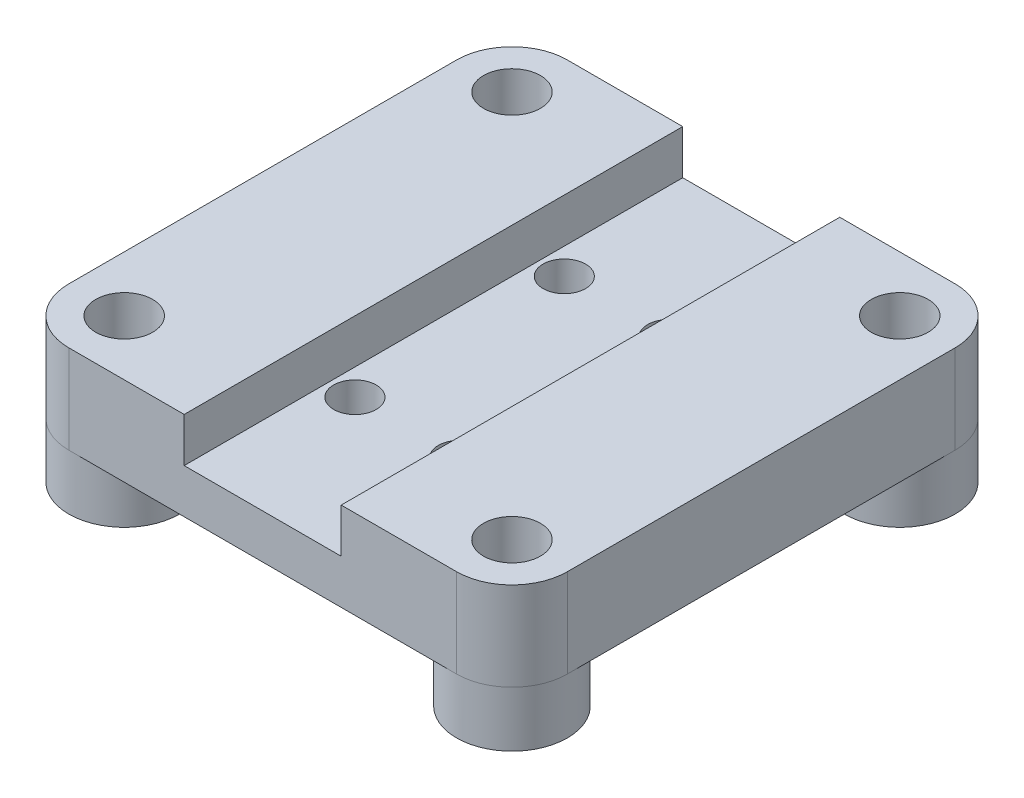
SolidWorks part; units mm, degrees
material "ABS"
ref_plane "Front Plane" through (0, 0, 0) normal (0, 0, 1) x (1, 0, 0)
ref_plane "Top Plane" through (0, 0, 0) normal (0, 1, 0) x (1, 0, 0)
ref_plane "Right Plane" through (0, 0, 0) normal (1, 0, 0) x (0, 0, -1)
sketch "Sketch2" plane through (0, 0, 0) normal (0, 0, 1) x (1, 0, 0)
  line L0 (-14.2875, 0) -> (-14.2875, 5.08)
  line L1 (-14.2875, 5.08) -> (-4.5, 5.08)
  line L2 (-4.5, 5.08) -> (-4.5, 2.54)
  line L3 (-4.5, 2.54) -> (4.5, 2.54)
  line L4 (4.5, 2.54) -> (4.5, 5.08)
  line L5 (4.5, 5.08) -> (14.2875, 5.08)
  line L6 (14.2875, 5.08) -> (14.2875, 0)
  line L7 (14.2875, 0) -> (-14.2875, 0)
  dimension "D1" = 2.54
  dimension "D2" = 9
  dimension "D3" = 2.54
  dimension "D4" = 28.575
extrude "Boss-Extrude1" add sketch "Sketch2" along normal mid plane 28.575
hole_wizard "#4 Clearance Hole1" positions "Sketch3" profile "Sketch5" hole size "#4" standard "ANSI Inch" end condition through all
sketch "Sketch3" plane through (0, 5.08, 0) normal (0, 1, 0) x (1, 0, 0)
  line L1 (11.1125, -11.1125) -> (-11.1125, -11.1125)
  line L2 (11.1125, -11.1125) -> (11.1125, 11.1125)
  line L3 (11.1125, 11.1125) -> (-11.1125, 11.1125)
  line L4 (-11.1125, -11.1125) -> (-11.1125, 11.1125)
  line L5 (11.1125, -11.1125) -> (-11.1125, 11.1125) construction
  line L6 (11.1125, 11.1125) -> (-11.1125, -11.1125) construction
  point P2 (-11.1125, 11.1125)
  point P33 (11.1125, -11.1125)
  point P34 (11.1125, 11.1125)
  point P35 (-11.1125, -11.1125)
  dimension "D1" = 22.225
sketch "Sketch5" plane through (-11.1125, 5.08, -11.1125) normal (1, 0, 0) x (0, 0, 1)
  line L0 (0, 0) -> (0, 5.08)
  line L1 (0, 5.08) -> (1.6319, 5.08)
  line L2 (1.6319, 5.08) -> (1.6319, 0)
  line L5 (1.6319, 0) -> (0, 0)
  line L11 (0, -6.35) -> (0, 107.95) construction
  dimension "Thru Hole Dia." = 3.2639
  dimension "Thru Hole Depth" = 5.08
sketch "Sketch6" plane through (0, 0, 0) normal (0, -1, 0) x (1, 0, 0)
  line L0 (-14.2875, 14.2875) -> (14.2875, 14.2875) construction
  circle A0 centre (-11.1125, 11.1125) radius 3.175
  circle A1 centre (11.1125, 11.1125) radius 3.175
  circle A2 centre (11.1125, -11.1125) radius 3.175
  circle A3 centre (-11.1125, -11.1125) radius 3.175
  circle A4 centre (-11.1125, -11.1125) radius 1.6319 construction
  circle A5 centre (11.1125, -11.1125) radius 1.6319 construction
  circle A6 centre (11.1125, 11.1125) radius 1.6319 construction
  circle A7 centre (-11.1125, 11.1125) radius 1.6319 construction
  circle A8 centre (-11.1125, -11.1125) radius 1.6319
  circle A9 centre (11.1125, -11.1125) radius 1.6319
  circle A10 centre (11.1125, 11.1125) radius 1.6319
  circle A11 centre (-11.1125, 11.1125) radius 1.6319
extrude "Boss-Extrude2" add sketch "Sketch6" along normal blind 3.175
fillet "Fillet1" radius 3.175 4 edges at (-14.2875, 2.54, -14.2875) (-14.2875, 2.54, 14.2875) (14.2875, 2.54, -14.2875) (14.2875, 2.54, 14.2875)
hole_wizard "#2 Clearance Hole2" positions "Sketch7" profile "Sketch8" hole size "#2" standard "ANSI Inch" end condition through all
sketch "Sketch7" plane through (0, 2.54, 0) normal (0, 1, 0) x (1, 0, 0)
  line L2 (3, -6) -> (-3, -6)
  line L3 (3, -6) -> (3, 6)
  line L4 (3, 6) -> (-3, 6)
  line L5 (-3, -6) -> (-3, 6)
  line L6 (3, -6) -> (-3, 6) construction
  line L7 (3, 6) -> (-3, -6) construction
  point P52 (-3, 6)
  point P75 (3, -6)
  point P76 (3, 6)
  point P77 (-3, -6)
  dimension "D1" = 6
  dimension "D2" = 12
sketch "Sketch8" plane through (-3, 2.54, -6) normal (1, 0, 0) x (0, 0, 1)
  line L0 (0, 0) -> (0, 5.715)
  line L1 (0, 5.715) -> (1.2192, 5.715)
  line L2 (1.2192, 5.715) -> (1.2192, 0)
  line L5 (1.2192, 0) -> (0, 0)
  line L11 (0, -6.35) -> (0, 107.95) construction
  dimension "Thru Hole Dia." = 2.4384
  dimension "Thru Hole Depth" = 5.715
equation "\"D1@Sketch7\"=6mm"
equation "\"D2@Sketch7\"=12mm"
